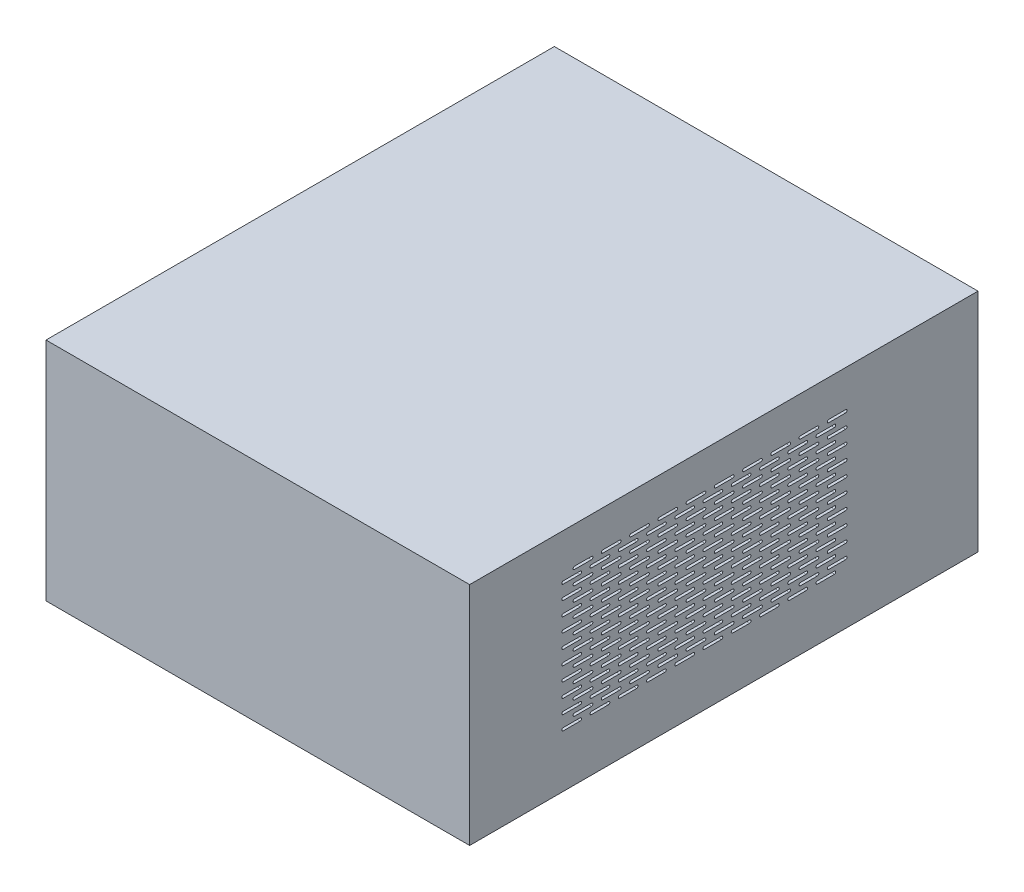
SolidWorks part; units mm, degrees
ref_plane "前视基准面" through (0, 0, 0) normal (0, 0, 1) x (1, 0, 0)
ref_plane "上视基准面" through (0, 0, 0) normal (0, 1, 0) x (1, 0, 0)
ref_plane "右视基准面" through (0, 0, 0) normal (1, 0, 0) x (0, 0, -1)
sketch "草图1" plane through (0, 0, 0) normal (0, 0, 1) x (1, 0, 0)
  line L1 (-75, 40) -> (75, 40)
  line L2 (-75, 40) -> (-75, -40)
  line L3 (-75, -40) -> (75, -40)
  line L4 (75, 40) -> (75, -40)
  line L5 (-75, 40) -> (75, -40) construction
  line L6 (-75, -40) -> (75, 40) construction
  point P0 (0, 0)
  dimension "D1" = 150
  dimension "D2" = 80
extrude "凸台-拉伸1" add sketch "草图1" along normal blind 90 and the other way blind 90 contours L1 L4 L3 L2
shell "抽壳1" thickness 2.3 removed face at (0, 0, -90)
sketch "草图2" plane through (75, 0, 0) normal (1, 0, 0) x (0, 0, -1)
  line L0 (-46.8721, 27.0767) -> (-52.8721, 27.0767)
  line L1 (-46.8721, 26.0767) -> (-52.8721, 26.0767)
  line L2 (-36.8721, 27.0767) -> (-42.8721, 27.0767)
  line L3 (-36.8721, 26.0767) -> (-42.8721, 26.0767)
  line L4 (-26.8721, 27.0767) -> (-32.8721, 27.0767)
  line L5 (-26.8721, 26.0767) -> (-32.8721, 26.0767)
  line L6 (-16.8721, 27.0767) -> (-22.8721, 27.0767)
  line L7 (-16.8721, 26.0767) -> (-22.8721, 26.0767)
  line L8 (-6.8721, 27.0767) -> (-12.8721, 27.0767)
  line L9 (-6.8721, 26.0767) -> (-12.8721, 26.0767)
  line L10 (3.1279, 27.0767) -> (-2.8721, 27.0767)
  line L11 (3.1279, 26.0767) -> (-2.8721, 26.0767)
  line L12 (13.1279, 27.0767) -> (7.1279, 27.0767)
  line L13 (13.1279, 26.0767) -> (7.1279, 26.0767)
  line L14 (23.1279, 27.0767) -> (17.1279, 27.0767)
  line L15 (23.1279, 26.0767) -> (17.1279, 26.0767)
  line L16 (33.1279, 27.0767) -> (27.1279, 27.0767)
  line L17 (33.1279, 26.0767) -> (27.1279, 26.0767)
  line L18 (43.1279, 27.0767) -> (37.1279, 27.0767)
  line L19 (43.1279, 26.0767) -> (37.1279, 26.0767)
  line L20 (-50.8721, 24.5767) -> (-56.8721, 24.5767)
  line L21 (-50.8721, 23.5767) -> (-56.8721, 23.5767)
  line L22 (-40.8721, 24.5767) -> (-46.8721, 24.5767)
  line L23 (-40.8721, 23.5767) -> (-46.8721, 23.5767)
  line L24 (-30.8721, 24.5767) -> (-36.8721, 24.5767)
  line L25 (-30.8721, 23.5767) -> (-36.8721, 23.5767)
  line L26 (-20.8721, 24.5767) -> (-26.8721, 24.5767)
  line L27 (-20.8721, 23.5767) -> (-26.8721, 23.5767)
  line L28 (-10.8721, 24.5767) -> (-16.8721, 24.5767)
  line L29 (-10.8721, 23.5767) -> (-16.8721, 23.5767)
  line L30 (-0.8721, 24.5767) -> (-6.8721, 24.5767)
  line L31 (-0.8721, 23.5767) -> (-6.8721, 23.5767)
  line L32 (9.1279, 24.5767) -> (3.1279, 24.5767)
  line L33 (9.1279, 23.5767) -> (3.1279, 23.5767)
  line L34 (19.1279, 24.5767) -> (13.1279, 24.5767)
  line L35 (19.1279, 23.5767) -> (13.1279, 23.5767)
  line L36 (29.1279, 24.5767) -> (23.1279, 24.5767)
  line L37 (29.1279, 23.5767) -> (23.1279, 23.5767)
  line L38 (39.1279, 24.5767) -> (33.1279, 24.5767)
  line L39 (39.1279, 23.5767) -> (33.1279, 23.5767)
  line L40 (-46.8721, 22.0767) -> (-52.8721, 22.0767)
  line L41 (-46.8721, 21.0767) -> (-52.8721, 21.0767)
  line L42 (-36.8721, 22.0767) -> (-42.8721, 22.0767)
  line L43 (-36.8721, 21.0767) -> (-42.8721, 21.0767)
  line L44 (-26.8721, 22.0767) -> (-32.8721, 22.0767)
  line L45 (-26.8721, 21.0767) -> (-32.8721, 21.0767)
  line L46 (-16.8721, 22.0767) -> (-22.8721, 22.0767)
  line L47 (-16.8721, 21.0767) -> (-22.8721, 21.0767)
  line L48 (-6.8721, 22.0767) -> (-12.8721, 22.0767)
  line L49 (-6.8721, 21.0767) -> (-12.8721, 21.0767)
  line L50 (3.1279, 22.0767) -> (-2.8721, 22.0767)
  line L51 (3.1279, 21.0767) -> (-2.8721, 21.0767)
  line L52 (13.1279, 22.0767) -> (7.1279, 22.0767)
  line L53 (13.1279, 21.0767) -> (7.1279, 21.0767)
  line L54 (23.1279, 22.0767) -> (17.1279, 22.0767)
  line L55 (23.1279, 21.0767) -> (17.1279, 21.0767)
  line L56 (33.1279, 22.0767) -> (27.1279, 22.0767)
  line L57 (33.1279, 21.0767) -> (27.1279, 21.0767)
  line L58 (43.1279, 22.0767) -> (37.1279, 22.0767)
  line L59 (43.1279, 21.0767) -> (37.1279, 21.0767)
  line L60 (-50.8721, 19.5767) -> (-56.8721, 19.5767)
  line L61 (-50.8721, 18.5767) -> (-56.8721, 18.5767)
  line L62 (-40.8721, 19.5767) -> (-46.8721, 19.5767)
  line L63 (-40.8721, 18.5767) -> (-46.8721, 18.5767)
  line L64 (-30.8721, 19.5767) -> (-36.8721, 19.5767)
  line L65 (-30.8721, 18.5767) -> (-36.8721, 18.5767)
  line L66 (-20.8721, 19.5767) -> (-26.8721, 19.5767)
  line L67 (-20.8721, 18.5767) -> (-26.8721, 18.5767)
  line L68 (-10.8721, 19.5767) -> (-16.8721, 19.5767)
  line L69 (-10.8721, 18.5767) -> (-16.8721, 18.5767)
  line L70 (-0.8721, 19.5767) -> (-6.8721, 19.5767)
  line L71 (-0.8721, 18.5767) -> (-6.8721, 18.5767)
  line L72 (9.1279, 19.5767) -> (3.1279, 19.5767)
  line L73 (9.1279, 18.5767) -> (3.1279, 18.5767)
  line L74 (19.1279, 19.5767) -> (13.1279, 19.5767)
  line L75 (19.1279, 18.5767) -> (13.1279, 18.5767)
  line L76 (29.1279, 19.5767) -> (23.1279, 19.5767)
  line L77 (29.1279, 18.5767) -> (23.1279, 18.5767)
  line L78 (39.1279, 19.5767) -> (33.1279, 19.5767)
  line L79 (39.1279, 18.5767) -> (33.1279, 18.5767)
  line L80 (-46.8721, 17.0767) -> (-52.8721, 17.0767)
  line L81 (-46.8721, 16.0767) -> (-52.8721, 16.0767)
  line L82 (-36.8721, 17.0767) -> (-42.8721, 17.0767)
  line L83 (-36.8721, 16.0767) -> (-42.8721, 16.0767)
  line L84 (-26.8721, 17.0767) -> (-32.8721, 17.0767)
  line L85 (-26.8721, 16.0767) -> (-32.8721, 16.0767)
  line L86 (-16.8721, 17.0767) -> (-22.8721, 17.0767)
  line L87 (-16.8721, 16.0767) -> (-22.8721, 16.0767)
  line L88 (-6.8721, 17.0767) -> (-12.8721, 17.0767)
  line L89 (-6.8721, 16.0767) -> (-12.8721, 16.0767)
  line L90 (3.1279, 17.0767) -> (-2.8721, 17.0767)
  line L91 (3.1279, 16.0767) -> (-2.8721, 16.0767)
  line L92 (13.1279, 17.0767) -> (7.1279, 17.0767)
  line L93 (13.1279, 16.0767) -> (7.1279, 16.0767)
  line L94 (23.1279, 17.0767) -> (17.1279, 17.0767)
  line L95 (23.1279, 16.0767) -> (17.1279, 16.0767)
  line L96 (33.1279, 17.0767) -> (27.1279, 17.0767)
  line L97 (33.1279, 16.0767) -> (27.1279, 16.0767)
  line L98 (43.1279, 17.0767) -> (37.1279, 17.0767)
  line L99 (43.1279, 16.0767) -> (37.1279, 16.0767)
  line L100 (-50.8721, 14.5767) -> (-56.8721, 14.5767)
  line L101 (-50.8721, 13.5767) -> (-56.8721, 13.5767)
  line L102 (-40.8721, 14.5767) -> (-46.8721, 14.5767)
  line L103 (-40.8721, 13.5767) -> (-46.8721, 13.5767)
  line L104 (-30.8721, 14.5767) -> (-36.8721, 14.5767)
  line L105 (-30.8721, 13.5767) -> (-36.8721, 13.5767)
  line L106 (-20.8721, 14.5767) -> (-26.8721, 14.5767)
  line L107 (-20.8721, 13.5767) -> (-26.8721, 13.5767)
  line L108 (-10.8721, 14.5767) -> (-16.8721, 14.5767)
  line L109 (-10.8721, 13.5767) -> (-16.8721, 13.5767)
  line L110 (-0.8721, 14.5767) -> (-6.8721, 14.5767)
  line L111 (-0.8721, 13.5767) -> (-6.8721, 13.5767)
  line L112 (9.1279, 14.5767) -> (3.1279, 14.5767)
  line L113 (9.1279, 13.5767) -> (3.1279, 13.5767)
  line L114 (19.1279, 14.5767) -> (13.1279, 14.5767)
  line L115 (19.1279, 13.5767) -> (13.1279, 13.5767)
  line L116 (29.1279, 14.5767) -> (23.1279, 14.5767)
  line L117 (29.1279, 13.5767) -> (23.1279, 13.5767)
  line L118 (39.1279, 14.5767) -> (33.1279, 14.5767)
  line L119 (39.1279, 13.5767) -> (33.1279, 13.5767)
  line L120 (-46.8721, 12.0767) -> (-52.8721, 12.0767)
  line L121 (-46.8721, 11.0767) -> (-52.8721, 11.0767)
  line L122 (-36.8721, 12.0767) -> (-42.8721, 12.0767)
  line L123 (-36.8721, 11.0767) -> (-42.8721, 11.0767)
  line L124 (-26.8721, 12.0767) -> (-32.8721, 12.0767)
  line L125 (-26.8721, 11.0767) -> (-32.8721, 11.0767)
  line L126 (-16.8721, 12.0767) -> (-22.8721, 12.0767)
  line L127 (-16.8721, 11.0767) -> (-22.8721, 11.0767)
  line L128 (-6.8721, 12.0767) -> (-12.8721, 12.0767)
  line L129 (-6.8721, 11.0767) -> (-12.8721, 11.0767)
  line L130 (3.1279, 12.0767) -> (-2.8721, 12.0767)
  line L131 (3.1279, 11.0767) -> (-2.8721, 11.0767)
  line L132 (13.1279, 12.0767) -> (7.1279, 12.0767)
  line L133 (13.1279, 11.0767) -> (7.1279, 11.0767)
  line L134 (23.1279, 12.0767) -> (17.1279, 12.0767)
  line L135 (23.1279, 11.0767) -> (17.1279, 11.0767)
  line L136 (33.1279, 12.0767) -> (27.1279, 12.0767)
  line L137 (33.1279, 11.0767) -> (27.1279, 11.0767)
  line L138 (43.1279, 12.0767) -> (37.1279, 12.0767)
  line L139 (43.1279, 11.0767) -> (37.1279, 11.0767)
  line L140 (-50.8721, 9.5767) -> (-56.8721, 9.5767)
  line L141 (-50.8721, 8.5767) -> (-56.8721, 8.5767)
  line L142 (-40.8721, 9.5767) -> (-46.8721, 9.5767)
  line L143 (-40.8721, 8.5767) -> (-46.8721, 8.5767)
  line L144 (-30.8721, 9.5767) -> (-36.8721, 9.5767)
  line L145 (-30.8721, 8.5767) -> (-36.8721, 8.5767)
  line L146 (-20.8721, 9.5767) -> (-26.8721, 9.5767)
  line L147 (-20.8721, 8.5767) -> (-26.8721, 8.5767)
  line L148 (-10.8721, 9.5767) -> (-16.8721, 9.5767)
  line L149 (-10.8721, 8.5767) -> (-16.8721, 8.5767)
  line L150 (-0.8721, 9.5767) -> (-6.8721, 9.5767)
  line L151 (-0.8721, 8.5767) -> (-6.8721, 8.5767)
  line L152 (9.1279, 9.5767) -> (3.1279, 9.5767)
  line L153 (9.1279, 8.5767) -> (3.1279, 8.5767)
  line L154 (19.1279, 9.5767) -> (13.1279, 9.5767)
  line L155 (19.1279, 8.5767) -> (13.1279, 8.5767)
  line L156 (29.1279, 9.5767) -> (23.1279, 9.5767)
  line L157 (29.1279, 8.5767) -> (23.1279, 8.5767)
  line L158 (39.1279, 9.5767) -> (33.1279, 9.5767)
  line L159 (39.1279, 8.5767) -> (33.1279, 8.5767)
  line L160 (-46.8721, 7.0767) -> (-52.8721, 7.0767)
  line L161 (-46.8721, 6.0767) -> (-52.8721, 6.0767)
  line L162 (-36.8721, 7.0767) -> (-42.8721, 7.0767)
  line L163 (-36.8721, 6.0767) -> (-42.8721, 6.0767)
  line L164 (-26.8721, 7.0767) -> (-32.8721, 7.0767)
  line L165 (-26.8721, 6.0767) -> (-32.8721, 6.0767)
  line L166 (-16.8721, 7.0767) -> (-22.8721, 7.0767)
  line L167 (-16.8721, 6.0767) -> (-22.8721, 6.0767)
  line L168 (-6.8721, 7.0767) -> (-12.8721, 7.0767)
  line L169 (-6.8721, 6.0767) -> (-12.8721, 6.0767)
  line L170 (3.1279, 7.0767) -> (-2.8721, 7.0767)
  line L171 (3.1279, 6.0767) -> (-2.8721, 6.0767)
  line L172 (13.1279, 7.0767) -> (7.1279, 7.0767)
  line L173 (13.1279, 6.0767) -> (7.1279, 6.0767)
  line L174 (23.1279, 7.0767) -> (17.1279, 7.0767)
  line L175 (23.1279, 6.0767) -> (17.1279, 6.0767)
  line L176 (33.1279, 7.0767) -> (27.1279, 7.0767)
  line L177 (33.1279, 6.0767) -> (27.1279, 6.0767)
  line L178 (43.1279, 7.0767) -> (37.1279, 7.0767)
  line L179 (43.1279, 6.0767) -> (37.1279, 6.0767)
  line L180 (-50.8721, 4.5767) -> (-56.8721, 4.5767)
  line L181 (-50.8721, 3.5767) -> (-56.8721, 3.5767)
  line L182 (-40.8721, 4.5767) -> (-46.8721, 4.5767)
  line L183 (-40.8721, 3.5767) -> (-46.8721, 3.5767)
  line L184 (-30.8721, 4.5767) -> (-36.8721, 4.5767)
  line L185 (-30.8721, 3.5767) -> (-36.8721, 3.5767)
  line L186 (-20.8721, 4.5767) -> (-26.8721, 4.5767)
  line L187 (-20.8721, 3.5767) -> (-26.8721, 3.5767)
  line L188 (-10.8721, 4.5767) -> (-16.8721, 4.5767)
  line L189 (-10.8721, 3.5767) -> (-16.8721, 3.5767)
  line L190 (-0.8721, 4.5767) -> (-6.8721, 4.5767)
  line L191 (-0.8721, 3.5767) -> (-6.8721, 3.5767)
  line L192 (9.1279, 4.5767) -> (3.1279, 4.5767)
  line L193 (9.1279, 3.5767) -> (3.1279, 3.5767)
  line L194 (19.1279, 4.5767) -> (13.1279, 4.5767)
  line L195 (19.1279, 3.5767) -> (13.1279, 3.5767)
  line L196 (29.1279, 4.5767) -> (23.1279, 4.5767)
  line L197 (29.1279, 3.5767) -> (23.1279, 3.5767)
  line L198 (39.1279, 4.5767) -> (33.1279, 4.5767)
  line L199 (39.1279, 3.5767) -> (33.1279, 3.5767)
  line L200 (-46.8721, 2.0767) -> (-52.8721, 2.0767)
  line L201 (-46.8721, 1.0767) -> (-52.8721, 1.0767)
  line L202 (-36.8721, 2.0767) -> (-42.8721, 2.0767)
  line L203 (-36.8721, 1.0767) -> (-42.8721, 1.0767)
  line L204 (-26.8721, 2.0767) -> (-32.8721, 2.0767)
  line L205 (-26.8721, 1.0767) -> (-32.8721, 1.0767)
  line L206 (-16.8721, 2.0767) -> (-22.8721, 2.0767)
  line L207 (-16.8721, 1.0767) -> (-22.8721, 1.0767)
  line L208 (-6.8721, 2.0767) -> (-12.8721, 2.0767)
  line L209 (-6.8721, 1.0767) -> (-12.8721, 1.0767)
  line L210 (3.1279, 2.0767) -> (-2.8721, 2.0767)
  line L211 (3.1279, 1.0767) -> (-2.8721, 1.0767)
  line L212 (13.1279, 2.0767) -> (7.1279, 2.0767)
  line L213 (13.1279, 1.0767) -> (7.1279, 1.0767)
  line L214 (23.1279, 2.0767) -> (17.1279, 2.0767)
  line L215 (23.1279, 1.0767) -> (17.1279, 1.0767)
  line L216 (33.1279, 2.0767) -> (27.1279, 2.0767)
  line L217 (33.1279, 1.0767) -> (27.1279, 1.0767)
  line L218 (43.1279, 2.0767) -> (37.1279, 2.0767)
  line L219 (43.1279, 1.0767) -> (37.1279, 1.0767)
  line L220 (-50.8721, -0.4233) -> (-56.8721, -0.4233)
  line L221 (-50.8721, -1.4233) -> (-56.8721, -1.4233)
  line L222 (-40.8721, -0.4233) -> (-46.8721, -0.4233)
  line L223 (-40.8721, -1.4233) -> (-46.8721, -1.4233)
  line L224 (-30.8721, -0.4233) -> (-36.8721, -0.4233)
  line L225 (-30.8721, -1.4233) -> (-36.8721, -1.4233)
  line L226 (-20.8721, -0.4233) -> (-26.8721, -0.4233)
  line L227 (-20.8721, -1.4233) -> (-26.8721, -1.4233)
  line L228 (-10.8721, -0.4233) -> (-16.8721, -0.4233)
  line L229 (-10.8721, -1.4233) -> (-16.8721, -1.4233)
  line L230 (-0.8721, -0.4233) -> (-6.8721, -0.4233)
  line L231 (-0.8721, -1.4233) -> (-6.8721, -1.4233)
  line L232 (9.1279, -0.4233) -> (3.1279, -0.4233)
  line L233 (9.1279, -1.4233) -> (3.1279, -1.4233)
  line L234 (19.1279, -0.4233) -> (13.1279, -0.4233)
  line L235 (19.1279, -1.4233) -> (13.1279, -1.4233)
  line L236 (29.1279, -0.4233) -> (23.1279, -0.4233)
  line L237 (29.1279, -1.4233) -> (23.1279, -1.4233)
  line L238 (39.1279, -0.4233) -> (33.1279, -0.4233)
  line L239 (39.1279, -1.4233) -> (33.1279, -1.4233)
  line L240 (-46.8721, -2.9233) -> (-52.8721, -2.9233)
  line L241 (-46.8721, -3.9233) -> (-52.8721, -3.9233)
  line L242 (-36.8721, -2.9233) -> (-42.8721, -2.9233)
  line L243 (-36.8721, -3.9233) -> (-42.8721, -3.9233)
  line L244 (-26.8721, -2.9233) -> (-32.8721, -2.9233)
  line L245 (-26.8721, -3.9233) -> (-32.8721, -3.9233)
  line L246 (-16.8721, -2.9233) -> (-22.8721, -2.9233)
  line L247 (-16.8721, -3.9233) -> (-22.8721, -3.9233)
  line L248 (-6.8721, -2.9233) -> (-12.8721, -2.9233)
  line L249 (-6.8721, -3.9233) -> (-12.8721, -3.9233)
  line L250 (3.1279, -2.9233) -> (-2.8721, -2.9233)
  line L251 (3.1279, -3.9233) -> (-2.8721, -3.9233)
  line L252 (13.1279, -2.9233) -> (7.1279, -2.9233)
  line L253 (13.1279, -3.9233) -> (7.1279, -3.9233)
  line L254 (23.1279, -2.9233) -> (17.1279, -2.9233)
  line L255 (23.1279, -3.9233) -> (17.1279, -3.9233)
  line L256 (33.1279, -2.9233) -> (27.1279, -2.9233)
  line L257 (33.1279, -3.9233) -> (27.1279, -3.9233)
  line L258 (43.1279, -2.9233) -> (37.1279, -2.9233)
  line L259 (43.1279, -3.9233) -> (37.1279, -3.9233)
  line L260 (-50.8721, -5.4233) -> (-56.8721, -5.4233)
  line L261 (-50.8721, -6.4233) -> (-56.8721, -6.4233)
  line L262 (-40.8721, -5.4233) -> (-46.8721, -5.4233)
  line L263 (-40.8721, -6.4233) -> (-46.8721, -6.4233)
  line L264 (-30.8721, -5.4233) -> (-36.8721, -5.4233)
  line L265 (-30.8721, -6.4233) -> (-36.8721, -6.4233)
  line L266 (-20.8721, -5.4233) -> (-26.8721, -5.4233)
  line L267 (-20.8721, -6.4233) -> (-26.8721, -6.4233)
  line L268 (-10.8721, -5.4233) -> (-16.8721, -5.4233)
  line L269 (-10.8721, -6.4233) -> (-16.8721, -6.4233)
  line L270 (-0.8721, -5.4233) -> (-6.8721, -5.4233)
  line L271 (-0.8721, -6.4233) -> (-6.8721, -6.4233)
  line L272 (9.1279, -5.4233) -> (3.1279, -5.4233)
  line L273 (9.1279, -6.4233) -> (3.1279, -6.4233)
  line L274 (19.1279, -5.4233) -> (13.1279, -5.4233)
  line L275 (19.1279, -6.4233) -> (13.1279, -6.4233)
  line L276 (29.1279, -5.4233) -> (23.1279, -5.4233)
  line L277 (29.1279, -6.4233) -> (23.1279, -6.4233)
  line L278 (39.1279, -5.4233) -> (33.1279, -5.4233)
  line L279 (39.1279, -6.4233) -> (33.1279, -6.4233)
  line L280 (-46.8721, -7.9233) -> (-52.8721, -7.9233)
  line L281 (-46.8721, -8.9233) -> (-52.8721, -8.9233)
  line L282 (-36.8721, -7.9233) -> (-42.8721, -7.9233)
  line L283 (-36.8721, -8.9233) -> (-42.8721, -8.9233)
  line L284 (-26.8721, -7.9233) -> (-32.8721, -7.9233)
  line L285 (-26.8721, -8.9233) -> (-32.8721, -8.9233)
  line L286 (-16.8721, -7.9233) -> (-22.8721, -7.9233)
  line L287 (-16.8721, -8.9233) -> (-22.8721, -8.9233)
  line L288 (-6.8721, -7.9233) -> (-12.8721, -7.9233)
  line L289 (-6.8721, -8.9233) -> (-12.8721, -8.9233)
  line L290 (3.1279, -7.9233) -> (-2.8721, -7.9233)
  line L291 (3.1279, -8.9233) -> (-2.8721, -8.9233)
  line L292 (13.1279, -7.9233) -> (7.1279, -7.9233)
  line L293 (13.1279, -8.9233) -> (7.1279, -8.9233)
  line L294 (23.1279, -7.9233) -> (17.1279, -7.9233)
  line L295 (23.1279, -8.9233) -> (17.1279, -8.9233)
  line L296 (33.1279, -7.9233) -> (27.1279, -7.9233)
  line L297 (33.1279, -8.9233) -> (27.1279, -8.9233)
  line L298 (43.1279, -7.9233) -> (37.1279, -7.9233)
  line L299 (43.1279, -8.9233) -> (37.1279, -8.9233)
  line L300 (-50.8721, -10.4233) -> (-56.8721, -10.4233)
  line L301 (-50.8721, -11.4233) -> (-56.8721, -11.4233)
  line L302 (-40.8721, -10.4233) -> (-46.8721, -10.4233)
  line L303 (-40.8721, -11.4233) -> (-46.8721, -11.4233)
  line L304 (-30.8721, -10.4233) -> (-36.8721, -10.4233)
  line L305 (-30.8721, -11.4233) -> (-36.8721, -11.4233)
  line L306 (-20.8721, -10.4233) -> (-26.8721, -10.4233)
  line L307 (-20.8721, -11.4233) -> (-26.8721, -11.4233)
  line L308 (-10.8721, -10.4233) -> (-16.8721, -10.4233)
  line L309 (-10.8721, -11.4233) -> (-16.8721, -11.4233)
  line L310 (-0.8721, -10.4233) -> (-6.8721, -10.4233)
  line L311 (-0.8721, -11.4233) -> (-6.8721, -11.4233)
  line L312 (9.1279, -10.4233) -> (3.1279, -10.4233)
  line L313 (9.1279, -11.4233) -> (3.1279, -11.4233)
  line L314 (19.1279, -10.4233) -> (13.1279, -10.4233)
  line L315 (19.1279, -11.4233) -> (13.1279, -11.4233)
  line L316 (29.1279, -10.4233) -> (23.1279, -10.4233)
  line L317 (29.1279, -11.4233) -> (23.1279, -11.4233)
  line L318 (39.1279, -10.4233) -> (33.1279, -10.4233)
  line L319 (39.1279, -11.4233) -> (33.1279, -11.4233)
  line L320 (-46.8721, -12.9233) -> (-52.8721, -12.9233)
  line L321 (-46.8721, -13.9233) -> (-52.8721, -13.9233)
  line L322 (-36.8721, -12.9233) -> (-42.8721, -12.9233)
  line L323 (-36.8721, -13.9233) -> (-42.8721, -13.9233)
  line L324 (-26.8721, -12.9233) -> (-32.8721, -12.9233)
  line L325 (-26.8721, -13.9233) -> (-32.8721, -13.9233)
  line L326 (-16.8721, -12.9233) -> (-22.8721, -12.9233)
  line L327 (-16.8721, -13.9233) -> (-22.8721, -13.9233)
  line L328 (-6.8721, -12.9233) -> (-12.8721, -12.9233)
  line L329 (-6.8721, -13.9233) -> (-12.8721, -13.9233)
  line L330 (3.1279, -12.9233) -> (-2.8721, -12.9233)
  line L331 (3.1279, -13.9233) -> (-2.8721, -13.9233)
  line L332 (13.1279, -12.9233) -> (7.1279, -12.9233)
  line L333 (13.1279, -13.9233) -> (7.1279, -13.9233)
  line L334 (23.1279, -12.9233) -> (17.1279, -12.9233)
  line L335 (23.1279, -13.9233) -> (17.1279, -13.9233)
  line L336 (33.1279, -12.9233) -> (27.1279, -12.9233)
  line L337 (33.1279, -13.9233) -> (27.1279, -13.9233)
  line L338 (43.1279, -12.9233) -> (37.1279, -12.9233)
  line L339 (43.1279, -13.9233) -> (37.1279, -13.9233)
  line L340 (-50.8721, -15.4233) -> (-56.8721, -15.4233)
  line L341 (-50.8721, -16.4233) -> (-56.8721, -16.4233)
  line L342 (-40.8721, -15.4233) -> (-46.8721, -15.4233)
  line L343 (-40.8721, -16.4233) -> (-46.8721, -16.4233)
  line L344 (-30.8721, -15.4233) -> (-36.8721, -15.4233)
  line L345 (-30.8721, -16.4233) -> (-36.8721, -16.4233)
  line L346 (-20.8721, -15.4233) -> (-26.8721, -15.4233)
  line L347 (-20.8721, -16.4233) -> (-26.8721, -16.4233)
  line L348 (-10.8721, -15.4233) -> (-16.8721, -15.4233)
  line L349 (-10.8721, -16.4233) -> (-16.8721, -16.4233)
  line L350 (-0.8721, -15.4233) -> (-6.8721, -15.4233)
  line L351 (-0.8721, -16.4233) -> (-6.8721, -16.4233)
  line L352 (9.1279, -15.4233) -> (3.1279, -15.4233)
  line L353 (9.1279, -16.4233) -> (3.1279, -16.4233)
  line L354 (19.1279, -15.4233) -> (13.1279, -15.4233)
  line L355 (19.1279, -16.4233) -> (13.1279, -16.4233)
  line L356 (29.1279, -15.4233) -> (23.1279, -15.4233)
  line L357 (29.1279, -16.4233) -> (23.1279, -16.4233)
  line L358 (39.1279, -15.4233) -> (33.1279, -15.4233)
  line L359 (39.1279, -16.4233) -> (33.1279, -16.4233)
  line L360 (-46.8721, -17.9233) -> (-52.8721, -17.9233)
  line L361 (-46.8721, -18.9233) -> (-52.8721, -18.9233)
  line L362 (-36.8721, -17.9233) -> (-42.8721, -17.9233)
  line L363 (-36.8721, -18.9233) -> (-42.8721, -18.9233)
  line L364 (-26.8721, -17.9233) -> (-32.8721, -17.9233)
  line L365 (-26.8721, -18.9233) -> (-32.8721, -18.9233)
  line L366 (-16.8721, -17.9233) -> (-22.8721, -17.9233)
  line L367 (-16.8721, -18.9233) -> (-22.8721, -18.9233)
  line L368 (-6.8721, -17.9233) -> (-12.8721, -17.9233)
  line L369 (-6.8721, -18.9233) -> (-12.8721, -18.9233)
  line L370 (3.1279, -17.9233) -> (-2.8721, -17.9233)
  line L371 (3.1279, -18.9233) -> (-2.8721, -18.9233)
  line L372 (13.1279, -17.9233) -> (7.1279, -17.9233)
  line L373 (13.1279, -18.9233) -> (7.1279, -18.9233)
  line L374 (23.1279, -17.9233) -> (17.1279, -17.9233)
  line L375 (23.1279, -18.9233) -> (17.1279, -18.9233)
  line L376 (33.1279, -17.9233) -> (27.1279, -17.9233)
  line L377 (33.1279, -18.9233) -> (27.1279, -18.9233)
  line L378 (43.1279, -17.9233) -> (37.1279, -17.9233)
  line L379 (43.1279, -18.9233) -> (37.1279, -18.9233)
  line L380 (-50.8721, -20.4233) -> (-56.8721, -20.4233)
  line L381 (-50.8721, -21.4233) -> (-56.8721, -21.4233)
  line L382 (-40.8721, -20.4233) -> (-46.8721, -20.4233)
  line L383 (-40.8721, -21.4233) -> (-46.8721, -21.4233)
  line L384 (-30.8721, -20.4233) -> (-36.8721, -20.4233)
  line L385 (-30.8721, -21.4233) -> (-36.8721, -21.4233)
  line L386 (-20.8721, -20.4233) -> (-26.8721, -20.4233)
  line L387 (-20.8721, -21.4233) -> (-26.8721, -21.4233)
  line L388 (-10.8721, -20.4233) -> (-16.8721, -20.4233)
  line L389 (-10.8721, -21.4233) -> (-16.8721, -21.4233)
  line L390 (-0.8721, -20.4233) -> (-6.8721, -20.4233)
  line L391 (-0.8721, -21.4233) -> (-6.8721, -21.4233)
  line L392 (9.1279, -20.4233) -> (3.1279, -20.4233)
  line L393 (9.1279, -21.4233) -> (3.1279, -21.4233)
  line L394 (19.1279, -20.4233) -> (13.1279, -20.4233)
  line L395 (19.1279, -21.4233) -> (13.1279, -21.4233)
  line L396 (29.1279, -20.4233) -> (23.1279, -20.4233)
  line L397 (29.1279, -21.4233) -> (23.1279, -21.4233)
  line L398 (39.1279, -20.4233) -> (33.1279, -20.4233)
  line L399 (39.1279, -21.4233) -> (33.1279, -21.4233)
  arc A0 (-46.8721, 26.0767) -> (-46.8721, 27.0767) centre (-46.8721, 26.5767) ccw
  arc A1 (-52.8721, 27.0767) -> (-52.8721, 26.0767) centre (-52.8721, 26.5767) ccw
  arc A2 (-36.8721, 26.0767) -> (-36.8721, 27.0767) centre (-36.8721, 26.5767) ccw
  arc A3 (-42.8721, 27.0767) -> (-42.8721, 26.0767) centre (-42.8721, 26.5767) ccw
  arc A4 (-26.8721, 26.0767) -> (-26.8721, 27.0767) centre (-26.8721, 26.5767) ccw
  arc A5 (-32.8721, 27.0767) -> (-32.8721, 26.0767) centre (-32.8721, 26.5767) ccw
  arc A6 (-16.8721, 26.0767) -> (-16.8721, 27.0767) centre (-16.8721, 26.5767) ccw
  arc A7 (-22.8721, 27.0767) -> (-22.8721, 26.0767) centre (-22.8721, 26.5767) ccw
  arc A8 (-6.8721, 26.0767) -> (-6.8721, 27.0767) centre (-6.8721, 26.5767) ccw
  arc A9 (-12.8721, 27.0767) -> (-12.8721, 26.0767) centre (-12.8721, 26.5767) ccw
  arc A10 (3.1279, 26.0767) -> (3.1279, 27.0767) centre (3.1279, 26.5767) ccw
  arc A11 (-2.8721, 27.0767) -> (-2.8721, 26.0767) centre (-2.8721, 26.5767) ccw
  arc A12 (13.1279, 26.0767) -> (13.1279, 27.0767) centre (13.1279, 26.5767) ccw
  arc A13 (7.1279, 27.0767) -> (7.1279, 26.0767) centre (7.1279, 26.5767) ccw
  arc A14 (23.1279, 26.0767) -> (23.1279, 27.0767) centre (23.1279, 26.5767) ccw
  arc A15 (17.1279, 27.0767) -> (17.1279, 26.0767) centre (17.1279, 26.5767) ccw
  arc A16 (33.1279, 26.0767) -> (33.1279, 27.0767) centre (33.1279, 26.5767) ccw
  arc A17 (27.1279, 27.0767) -> (27.1279, 26.0767) centre (27.1279, 26.5767) ccw
  arc A18 (43.1279, 26.0767) -> (43.1279, 27.0767) centre (43.1279, 26.5767) ccw
  arc A19 (37.1279, 27.0767) -> (37.1279, 26.0767) centre (37.1279, 26.5767) ccw
  arc A20 (-50.8721, 23.5767) -> (-50.8721, 24.5767) centre (-50.8721, 24.0767) ccw
  arc A21 (-56.8721, 24.5767) -> (-56.8721, 23.5767) centre (-56.8721, 24.0767) ccw
  arc A22 (-40.8721, 23.5767) -> (-40.8721, 24.5767) centre (-40.8721, 24.0767) ccw
  arc A23 (-46.8721, 24.5767) -> (-46.8721, 23.5767) centre (-46.8721, 24.0767) ccw
  arc A24 (-30.8721, 23.5767) -> (-30.8721, 24.5767) centre (-30.8721, 24.0767) ccw
  arc A25 (-36.8721, 24.5767) -> (-36.8721, 23.5767) centre (-36.8721, 24.0767) ccw
  arc A26 (-20.8721, 23.5767) -> (-20.8721, 24.5767) centre (-20.8721, 24.0767) ccw
  arc A27 (-26.8721, 24.5767) -> (-26.8721, 23.5767) centre (-26.8721, 24.0767) ccw
  arc A28 (-10.8721, 23.5767) -> (-10.8721, 24.5767) centre (-10.8721, 24.0767) ccw
  arc A29 (-16.8721, 24.5767) -> (-16.8721, 23.5767) centre (-16.8721, 24.0767) ccw
  arc A30 (-0.8721, 23.5767) -> (-0.8721, 24.5767) centre (-0.8721, 24.0767) ccw
  arc A31 (-6.8721, 24.5767) -> (-6.8721, 23.5767) centre (-6.8721, 24.0767) ccw
  arc A32 (9.1279, 23.5767) -> (9.1279, 24.5767) centre (9.1279, 24.0767) ccw
  arc A33 (3.1279, 24.5767) -> (3.1279, 23.5767) centre (3.1279, 24.0767) ccw
  arc A34 (19.1279, 23.5767) -> (19.1279, 24.5767) centre (19.1279, 24.0767) ccw
  arc A35 (13.1279, 24.5767) -> (13.1279, 23.5767) centre (13.1279, 24.0767) ccw
  arc A36 (29.1279, 23.5767) -> (29.1279, 24.5767) centre (29.1279, 24.0767) ccw
  arc A37 (23.1279, 24.5767) -> (23.1279, 23.5767) centre (23.1279, 24.0767) ccw
  arc A38 (39.1279, 23.5767) -> (39.1279, 24.5767) centre (39.1279, 24.0767) ccw
  arc A39 (33.1279, 24.5767) -> (33.1279, 23.5767) centre (33.1279, 24.0767) ccw
  arc A40 (-46.8721, 21.0767) -> (-46.8721, 22.0767) centre (-46.8721, 21.5767) ccw
  arc A41 (-52.8721, 22.0767) -> (-52.8721, 21.0767) centre (-52.8721, 21.5767) ccw
  arc A42 (-36.8721, 21.0767) -> (-36.8721, 22.0767) centre (-36.8721, 21.5767) ccw
  arc A43 (-42.8721, 22.0767) -> (-42.8721, 21.0767) centre (-42.8721, 21.5767) ccw
  arc A44 (-26.8721, 21.0767) -> (-26.8721, 22.0767) centre (-26.8721, 21.5767) ccw
  arc A45 (-32.8721, 22.0767) -> (-32.8721, 21.0767) centre (-32.8721, 21.5767) ccw
  arc A46 (-16.8721, 21.0767) -> (-16.8721, 22.0767) centre (-16.8721, 21.5767) ccw
  arc A47 (-22.8721, 22.0767) -> (-22.8721, 21.0767) centre (-22.8721, 21.5767) ccw
  arc A48 (-6.8721, 21.0767) -> (-6.8721, 22.0767) centre (-6.8721, 21.5767) ccw
  arc A49 (-12.8721, 22.0767) -> (-12.8721, 21.0767) centre (-12.8721, 21.5767) ccw
  arc A50 (3.1279, 21.0767) -> (3.1279, 22.0767) centre (3.1279, 21.5767) ccw
  arc A51 (-2.8721, 22.0767) -> (-2.8721, 21.0767) centre (-2.8721, 21.5767) ccw
  arc A52 (13.1279, 21.0767) -> (13.1279, 22.0767) centre (13.1279, 21.5767) ccw
  arc A53 (7.1279, 22.0767) -> (7.1279, 21.0767) centre (7.1279, 21.5767) ccw
  arc A54 (23.1279, 21.0767) -> (23.1279, 22.0767) centre (23.1279, 21.5767) ccw
  arc A55 (17.1279, 22.0767) -> (17.1279, 21.0767) centre (17.1279, 21.5767) ccw
  arc A56 (33.1279, 21.0767) -> (33.1279, 22.0767) centre (33.1279, 21.5767) ccw
  arc A57 (27.1279, 22.0767) -> (27.1279, 21.0767) centre (27.1279, 21.5767) ccw
  arc A58 (43.1279, 21.0767) -> (43.1279, 22.0767) centre (43.1279, 21.5767) ccw
  arc A59 (37.1279, 22.0767) -> (37.1279, 21.0767) centre (37.1279, 21.5767) ccw
  arc A60 (-50.8721, 18.5767) -> (-50.8721, 19.5767) centre (-50.8721, 19.0767) ccw
  arc A61 (-56.8721, 19.5767) -> (-56.8721, 18.5767) centre (-56.8721, 19.0767) ccw
  arc A62 (-40.8721, 18.5767) -> (-40.8721, 19.5767) centre (-40.8721, 19.0767) ccw
  arc A63 (-46.8721, 19.5767) -> (-46.8721, 18.5767) centre (-46.8721, 19.0767) ccw
  arc A64 (-30.8721, 18.5767) -> (-30.8721, 19.5767) centre (-30.8721, 19.0767) ccw
  arc A65 (-36.8721, 19.5767) -> (-36.8721, 18.5767) centre (-36.8721, 19.0767) ccw
  arc A66 (-20.8721, 18.5767) -> (-20.8721, 19.5767) centre (-20.8721, 19.0767) ccw
  arc A67 (-26.8721, 19.5767) -> (-26.8721, 18.5767) centre (-26.8721, 19.0767) ccw
  arc A68 (-10.8721, 18.5767) -> (-10.8721, 19.5767) centre (-10.8721, 19.0767) ccw
  arc A69 (-16.8721, 19.5767) -> (-16.8721, 18.5767) centre (-16.8721, 19.0767) ccw
  arc A70 (-0.8721, 18.5767) -> (-0.8721, 19.5767) centre (-0.8721, 19.0767) ccw
  arc A71 (-6.8721, 19.5767) -> (-6.8721, 18.5767) centre (-6.8721, 19.0767) ccw
  arc A72 (9.1279, 18.5767) -> (9.1279, 19.5767) centre (9.1279, 19.0767) ccw
  arc A73 (3.1279, 19.5767) -> (3.1279, 18.5767) centre (3.1279, 19.0767) ccw
  arc A74 (19.1279, 18.5767) -> (19.1279, 19.5767) centre (19.1279, 19.0767) ccw
  arc A75 (13.1279, 19.5767) -> (13.1279, 18.5767) centre (13.1279, 19.0767) ccw
  arc A76 (29.1279, 18.5767) -> (29.1279, 19.5767) centre (29.1279, 19.0767) ccw
  arc A77 (23.1279, 19.5767) -> (23.1279, 18.5767) centre (23.1279, 19.0767) ccw
  arc A78 (39.1279, 18.5767) -> (39.1279, 19.5767) centre (39.1279, 19.0767) ccw
  arc A79 (33.1279, 19.5767) -> (33.1279, 18.5767) centre (33.1279, 19.0767) ccw
  arc A80 (-46.8721, 16.0767) -> (-46.8721, 17.0767) centre (-46.8721, 16.5767) ccw
  arc A81 (-52.8721, 17.0767) -> (-52.8721, 16.0767) centre (-52.8721, 16.5767) ccw
  arc A82 (-36.8721, 16.0767) -> (-36.8721, 17.0767) centre (-36.8721, 16.5767) ccw
  arc A83 (-42.8721, 17.0767) -> (-42.8721, 16.0767) centre (-42.8721, 16.5767) ccw
  arc A84 (-26.8721, 16.0767) -> (-26.8721, 17.0767) centre (-26.8721, 16.5767) ccw
  arc A85 (-32.8721, 17.0767) -> (-32.8721, 16.0767) centre (-32.8721, 16.5767) ccw
  arc A86 (-16.8721, 16.0767) -> (-16.8721, 17.0767) centre (-16.8721, 16.5767) ccw
  arc A87 (-22.8721, 17.0767) -> (-22.8721, 16.0767) centre (-22.8721, 16.5767) ccw
  arc A88 (-6.8721, 16.0767) -> (-6.8721, 17.0767) centre (-6.8721, 16.5767) ccw
  arc A89 (-12.8721, 17.0767) -> (-12.8721, 16.0767) centre (-12.8721, 16.5767) ccw
  arc A90 (3.1279, 16.0767) -> (3.1279, 17.0767) centre (3.1279, 16.5767) ccw
  arc A91 (-2.8721, 17.0767) -> (-2.8721, 16.0767) centre (-2.8721, 16.5767) ccw
  arc A92 (13.1279, 16.0767) -> (13.1279, 17.0767) centre (13.1279, 16.5767) ccw
  arc A93 (7.1279, 17.0767) -> (7.1279, 16.0767) centre (7.1279, 16.5767) ccw
  arc A94 (23.1279, 16.0767) -> (23.1279, 17.0767) centre (23.1279, 16.5767) ccw
  arc A95 (17.1279, 17.0767) -> (17.1279, 16.0767) centre (17.1279, 16.5767) ccw
  arc A96 (33.1279, 16.0767) -> (33.1279, 17.0767) centre (33.1279, 16.5767) ccw
  arc A97 (27.1279, 17.0767) -> (27.1279, 16.0767) centre (27.1279, 16.5767) ccw
  arc A98 (43.1279, 16.0767) -> (43.1279, 17.0767) centre (43.1279, 16.5767) ccw
  arc A99 (37.1279, 17.0767) -> (37.1279, 16.0767) centre (37.1279, 16.5767) ccw
  arc A100 (-50.8721, 13.5767) -> (-50.8721, 14.5767) centre (-50.8721, 14.0767) ccw
  arc A101 (-56.8721, 14.5767) -> (-56.8721, 13.5767) centre (-56.8721, 14.0767) ccw
  arc A102 (-40.8721, 13.5767) -> (-40.8721, 14.5767) centre (-40.8721, 14.0767) ccw
  arc A103 (-46.8721, 14.5767) -> (-46.8721, 13.5767) centre (-46.8721, 14.0767) ccw
  arc A104 (-30.8721, 13.5767) -> (-30.8721, 14.5767) centre (-30.8721, 14.0767) ccw
  arc A105 (-36.8721, 14.5767) -> (-36.8721, 13.5767) centre (-36.8721, 14.0767) ccw
  arc A106 (-20.8721, 13.5767) -> (-20.8721, 14.5767) centre (-20.8721, 14.0767) ccw
  arc A107 (-26.8721, 14.5767) -> (-26.8721, 13.5767) centre (-26.8721, 14.0767) ccw
  arc A108 (-10.8721, 13.5767) -> (-10.8721, 14.5767) centre (-10.8721, 14.0767) ccw
  arc A109 (-16.8721, 14.5767) -> (-16.8721, 13.5767) centre (-16.8721, 14.0767) ccw
  arc A110 (-0.8721, 13.5767) -> (-0.8721, 14.5767) centre (-0.8721, 14.0767) ccw
  arc A111 (-6.8721, 14.5767) -> (-6.8721, 13.5767) centre (-6.8721, 14.0767) ccw
  arc A112 (9.1279, 13.5767) -> (9.1279, 14.5767) centre (9.1279, 14.0767) ccw
  arc A113 (3.1279, 14.5767) -> (3.1279, 13.5767) centre (3.1279, 14.0767) ccw
  arc A114 (19.1279, 13.5767) -> (19.1279, 14.5767) centre (19.1279, 14.0767) ccw
  arc A115 (13.1279, 14.5767) -> (13.1279, 13.5767) centre (13.1279, 14.0767) ccw
  arc A116 (29.1279, 13.5767) -> (29.1279, 14.5767) centre (29.1279, 14.0767) ccw
  arc A117 (23.1279, 14.5767) -> (23.1279, 13.5767) centre (23.1279, 14.0767) ccw
  arc A118 (39.1279, 13.5767) -> (39.1279, 14.5767) centre (39.1279, 14.0767) ccw
  arc A119 (33.1279, 14.5767) -> (33.1279, 13.5767) centre (33.1279, 14.0767) ccw
  arc A120 (-46.8721, 11.0767) -> (-46.8721, 12.0767) centre (-46.8721, 11.5767) ccw
  arc A121 (-52.8721, 12.0767) -> (-52.8721, 11.0767) centre (-52.8721, 11.5767) ccw
  arc A122 (-36.8721, 11.0767) -> (-36.8721, 12.0767) centre (-36.8721, 11.5767) ccw
  arc A123 (-42.8721, 12.0767) -> (-42.8721, 11.0767) centre (-42.8721, 11.5767) ccw
  arc A124 (-26.8721, 11.0767) -> (-26.8721, 12.0767) centre (-26.8721, 11.5767) ccw
  arc A125 (-32.8721, 12.0767) -> (-32.8721, 11.0767) centre (-32.8721, 11.5767) ccw
  arc A126 (-16.8721, 11.0767) -> (-16.8721, 12.0767) centre (-16.8721, 11.5767) ccw
  arc A127 (-22.8721, 12.0767) -> (-22.8721, 11.0767) centre (-22.8721, 11.5767) ccw
  arc A128 (-6.8721, 11.0767) -> (-6.8721, 12.0767) centre (-6.8721, 11.5767) ccw
  arc A129 (-12.8721, 12.0767) -> (-12.8721, 11.0767) centre (-12.8721, 11.5767) ccw
  arc A130 (3.1279, 11.0767) -> (3.1279, 12.0767) centre (3.1279, 11.5767) ccw
  arc A131 (-2.8721, 12.0767) -> (-2.8721, 11.0767) centre (-2.8721, 11.5767) ccw
  arc A132 (13.1279, 11.0767) -> (13.1279, 12.0767) centre (13.1279, 11.5767) ccw
  arc A133 (7.1279, 12.0767) -> (7.1279, 11.0767) centre (7.1279, 11.5767) ccw
  arc A134 (23.1279, 11.0767) -> (23.1279, 12.0767) centre (23.1279, 11.5767) ccw
  arc A135 (17.1279, 12.0767) -> (17.1279, 11.0767) centre (17.1279, 11.5767) ccw
  arc A136 (33.1279, 11.0767) -> (33.1279, 12.0767) centre (33.1279, 11.5767) ccw
  arc A137 (27.1279, 12.0767) -> (27.1279, 11.0767) centre (27.1279, 11.5767) ccw
  arc A138 (43.1279, 11.0767) -> (43.1279, 12.0767) centre (43.1279, 11.5767) ccw
  arc A139 (37.1279, 12.0767) -> (37.1279, 11.0767) centre (37.1279, 11.5767) ccw
  arc A140 (-50.8721, 8.5767) -> (-50.8721, 9.5767) centre (-50.8721, 9.0767) ccw
  arc A141 (-56.8721, 9.5767) -> (-56.8721, 8.5767) centre (-56.8721, 9.0767) ccw
  arc A142 (-40.8721, 8.5767) -> (-40.8721, 9.5767) centre (-40.8721, 9.0767) ccw
  arc A143 (-46.8721, 9.5767) -> (-46.8721, 8.5767) centre (-46.8721, 9.0767) ccw
  arc A144 (-30.8721, 8.5767) -> (-30.8721, 9.5767) centre (-30.8721, 9.0767) ccw
  arc A145 (-36.8721, 9.5767) -> (-36.8721, 8.5767) centre (-36.8721, 9.0767) ccw
  arc A146 (-20.8721, 8.5767) -> (-20.8721, 9.5767) centre (-20.8721, 9.0767) ccw
  arc A147 (-26.8721, 9.5767) -> (-26.8721, 8.5767) centre (-26.8721, 9.0767) ccw
  arc A148 (-10.8721, 8.5767) -> (-10.8721, 9.5767) centre (-10.8721, 9.0767) ccw
  arc A149 (-16.8721, 9.5767) -> (-16.8721, 8.5767) centre (-16.8721, 9.0767) ccw
  arc A150 (-0.8721, 8.5767) -> (-0.8721, 9.5767) centre (-0.8721, 9.0767) ccw
  arc A151 (-6.8721, 9.5767) -> (-6.8721, 8.5767) centre (-6.8721, 9.0767) ccw
  arc A152 (9.1279, 8.5767) -> (9.1279, 9.5767) centre (9.1279, 9.0767) ccw
  arc A153 (3.1279, 9.5767) -> (3.1279, 8.5767) centre (3.1279, 9.0767) ccw
  arc A154 (19.1279, 8.5767) -> (19.1279, 9.5767) centre (19.1279, 9.0767) ccw
  arc A155 (13.1279, 9.5767) -> (13.1279, 8.5767) centre (13.1279, 9.0767) ccw
  arc A156 (29.1279, 8.5767) -> (29.1279, 9.5767) centre (29.1279, 9.0767) ccw
  arc A157 (23.1279, 9.5767) -> (23.1279, 8.5767) centre (23.1279, 9.0767) ccw
  arc A158 (39.1279, 8.5767) -> (39.1279, 9.5767) centre (39.1279, 9.0767) ccw
  arc A159 (33.1279, 9.5767) -> (33.1279, 8.5767) centre (33.1279, 9.0767) ccw
  arc A160 (-46.8721, 6.0767) -> (-46.8721, 7.0767) centre (-46.8721, 6.5767) ccw
  arc A161 (-52.8721, 7.0767) -> (-52.8721, 6.0767) centre (-52.8721, 6.5767) ccw
  arc A162 (-36.8721, 6.0767) -> (-36.8721, 7.0767) centre (-36.8721, 6.5767) ccw
  arc A163 (-42.8721, 7.0767) -> (-42.8721, 6.0767) centre (-42.8721, 6.5767) ccw
  arc A164 (-26.8721, 6.0767) -> (-26.8721, 7.0767) centre (-26.8721, 6.5767) ccw
  arc A165 (-32.8721, 7.0767) -> (-32.8721, 6.0767) centre (-32.8721, 6.5767) ccw
  arc A166 (-16.8721, 6.0767) -> (-16.8721, 7.0767) centre (-16.8721, 6.5767) ccw
  arc A167 (-22.8721, 7.0767) -> (-22.8721, 6.0767) centre (-22.8721, 6.5767) ccw
  arc A168 (-6.8721, 6.0767) -> (-6.8721, 7.0767) centre (-6.8721, 6.5767) ccw
  arc A169 (-12.8721, 7.0767) -> (-12.8721, 6.0767) centre (-12.8721, 6.5767) ccw
  arc A170 (3.1279, 6.0767) -> (3.1279, 7.0767) centre (3.1279, 6.5767) ccw
  arc A171 (-2.8721, 7.0767) -> (-2.8721, 6.0767) centre (-2.8721, 6.5767) ccw
  arc A172 (13.1279, 6.0767) -> (13.1279, 7.0767) centre (13.1279, 6.5767) ccw
  arc A173 (7.1279, 7.0767) -> (7.1279, 6.0767) centre (7.1279, 6.5767) ccw
  arc A174 (23.1279, 6.0767) -> (23.1279, 7.0767) centre (23.1279, 6.5767) ccw
  arc A175 (17.1279, 7.0767) -> (17.1279, 6.0767) centre (17.1279, 6.5767) ccw
  arc A176 (33.1279, 6.0767) -> (33.1279, 7.0767) centre (33.1279, 6.5767) ccw
  arc A177 (27.1279, 7.0767) -> (27.1279, 6.0767) centre (27.1279, 6.5767) ccw
  arc A178 (43.1279, 6.0767) -> (43.1279, 7.0767) centre (43.1279, 6.5767) ccw
  arc A179 (37.1279, 7.0767) -> (37.1279, 6.0767) centre (37.1279, 6.5767) ccw
  arc A180 (-50.8721, 3.5767) -> (-50.8721, 4.5767) centre (-50.8721, 4.0767) ccw
  arc A181 (-56.8721, 4.5767) -> (-56.8721, 3.5767) centre (-56.8721, 4.0767) ccw
  arc A182 (-40.8721, 3.5767) -> (-40.8721, 4.5767) centre (-40.8721, 4.0767) ccw
  arc A183 (-46.8721, 4.5767) -> (-46.8721, 3.5767) centre (-46.8721, 4.0767) ccw
  arc A184 (-30.8721, 3.5767) -> (-30.8721, 4.5767) centre (-30.8721, 4.0767) ccw
  arc A185 (-36.8721, 4.5767) -> (-36.8721, 3.5767) centre (-36.8721, 4.0767) ccw
  arc A186 (-20.8721, 3.5767) -> (-20.8721, 4.5767) centre (-20.8721, 4.0767) ccw
  arc A187 (-26.8721, 4.5767) -> (-26.8721, 3.5767) centre (-26.8721, 4.0767) ccw
  arc A188 (-10.8721, 3.5767) -> (-10.8721, 4.5767) centre (-10.8721, 4.0767) ccw
  arc A189 (-16.8721, 4.5767) -> (-16.8721, 3.5767) centre (-16.8721, 4.0767) ccw
  arc A190 (-0.8721, 3.5767) -> (-0.8721, 4.5767) centre (-0.8721, 4.0767) ccw
  arc A191 (-6.8721, 4.5767) -> (-6.8721, 3.5767) centre (-6.8721, 4.0767) ccw
  arc A192 (9.1279, 3.5767) -> (9.1279, 4.5767) centre (9.1279, 4.0767) ccw
  arc A193 (3.1279, 4.5767) -> (3.1279, 3.5767) centre (3.1279, 4.0767) ccw
  arc A194 (19.1279, 3.5767) -> (19.1279, 4.5767) centre (19.1279, 4.0767) ccw
  arc A195 (13.1279, 4.5767) -> (13.1279, 3.5767) centre (13.1279, 4.0767) ccw
  arc A196 (29.1279, 3.5767) -> (29.1279, 4.5767) centre (29.1279, 4.0767) ccw
  arc A197 (23.1279, 4.5767) -> (23.1279, 3.5767) centre (23.1279, 4.0767) ccw
  arc A198 (39.1279, 3.5767) -> (39.1279, 4.5767) centre (39.1279, 4.0767) ccw
  arc A199 (33.1279, 4.5767) -> (33.1279, 3.5767) centre (33.1279, 4.0767) ccw
  arc A200 (-46.8721, 1.0767) -> (-46.8721, 2.0767) centre (-46.8721, 1.5767) ccw
  arc A201 (-52.8721, 2.0767) -> (-52.8721, 1.0767) centre (-52.8721, 1.5767) ccw
  arc A202 (-36.8721, 1.0767) -> (-36.8721, 2.0767) centre (-36.8721, 1.5767) ccw
  arc A203 (-42.8721, 2.0767) -> (-42.8721, 1.0767) centre (-42.8721, 1.5767) ccw
  arc A204 (-26.8721, 1.0767) -> (-26.8721, 2.0767) centre (-26.8721, 1.5767) ccw
  arc A205 (-32.8721, 2.0767) -> (-32.8721, 1.0767) centre (-32.8721, 1.5767) ccw
  arc A206 (-16.8721, 1.0767) -> (-16.8721, 2.0767) centre (-16.8721, 1.5767) ccw
  arc A207 (-22.8721, 2.0767) -> (-22.8721, 1.0767) centre (-22.8721, 1.5767) ccw
  arc A208 (-6.8721, 1.0767) -> (-6.8721, 2.0767) centre (-6.8721, 1.5767) ccw
  arc A209 (-12.8721, 2.0767) -> (-12.8721, 1.0767) centre (-12.8721, 1.5767) ccw
  arc A210 (3.1279, 1.0767) -> (3.1279, 2.0767) centre (3.1279, 1.5767) ccw
  arc A211 (-2.8721, 2.0767) -> (-2.8721, 1.0767) centre (-2.8721, 1.5767) ccw
  arc A212 (13.1279, 1.0767) -> (13.1279, 2.0767) centre (13.1279, 1.5767) ccw
  arc A213 (7.1279, 2.0767) -> (7.1279, 1.0767) centre (7.1279, 1.5767) ccw
  arc A214 (23.1279, 1.0767) -> (23.1279, 2.0767) centre (23.1279, 1.5767) ccw
  arc A215 (17.1279, 2.0767) -> (17.1279, 1.0767) centre (17.1279, 1.5767) ccw
  arc A216 (33.1279, 1.0767) -> (33.1279, 2.0767) centre (33.1279, 1.5767) ccw
  arc A217 (27.1279, 2.0767) -> (27.1279, 1.0767) centre (27.1279, 1.5767) ccw
  arc A218 (43.1279, 1.0767) -> (43.1279, 2.0767) centre (43.1279, 1.5767) ccw
  arc A219 (37.1279, 2.0767) -> (37.1279, 1.0767) centre (37.1279, 1.5767) ccw
  arc A220 (-50.8721, -1.4233) -> (-50.8721, -0.4233) centre (-50.8721, -0.9233) ccw
  arc A221 (-56.8721, -0.4233) -> (-56.8721, -1.4233) centre (-56.8721, -0.9233) ccw
  arc A222 (-40.8721, -1.4233) -> (-40.8721, -0.4233) centre (-40.8721, -0.9233) ccw
  arc A223 (-46.8721, -0.4233) -> (-46.8721, -1.4233) centre (-46.8721, -0.9233) ccw
  arc A224 (-30.8721, -1.4233) -> (-30.8721, -0.4233) centre (-30.8721, -0.9233) ccw
  arc A225 (-36.8721, -0.4233) -> (-36.8721, -1.4233) centre (-36.8721, -0.9233) ccw
  arc A226 (-20.8721, -1.4233) -> (-20.8721, -0.4233) centre (-20.8721, -0.9233) ccw
  arc A227 (-26.8721, -0.4233) -> (-26.8721, -1.4233) centre (-26.8721, -0.9233) ccw
  arc A228 (-10.8721, -1.4233) -> (-10.8721, -0.4233) centre (-10.8721, -0.9233) ccw
  arc A229 (-16.8721, -0.4233) -> (-16.8721, -1.4233) centre (-16.8721, -0.9233) ccw
  arc A230 (-0.8721, -1.4233) -> (-0.8721, -0.4233) centre (-0.8721, -0.9233) ccw
  arc A231 (-6.8721, -0.4233) -> (-6.8721, -1.4233) centre (-6.8721, -0.9233) ccw
  arc A232 (9.1279, -1.4233) -> (9.1279, -0.4233) centre (9.1279, -0.9233) ccw
  arc A233 (3.1279, -0.4233) -> (3.1279, -1.4233) centre (3.1279, -0.9233) ccw
  arc A234 (19.1279, -1.4233) -> (19.1279, -0.4233) centre (19.1279, -0.9233) ccw
  arc A235 (13.1279, -0.4233) -> (13.1279, -1.4233) centre (13.1279, -0.9233) ccw
  arc A236 (29.1279, -1.4233) -> (29.1279, -0.4233) centre (29.1279, -0.9233) ccw
  arc A237 (23.1279, -0.4233) -> (23.1279, -1.4233) centre (23.1279, -0.9233) ccw
  arc A238 (39.1279, -1.4233) -> (39.1279, -0.4233) centre (39.1279, -0.9233) ccw
  arc A239 (33.1279, -0.4233) -> (33.1279, -1.4233) centre (33.1279, -0.9233) ccw
  arc A240 (-46.8721, -3.9233) -> (-46.8721, -2.9233) centre (-46.8721, -3.4233) ccw
  arc A241 (-52.8721, -2.9233) -> (-52.8721, -3.9233) centre (-52.8721, -3.4233) ccw
  arc A242 (-36.8721, -3.9233) -> (-36.8721, -2.9233) centre (-36.8721, -3.4233) ccw
  arc A243 (-42.8721, -2.9233) -> (-42.8721, -3.9233) centre (-42.8721, -3.4233) ccw
  arc A244 (-26.8721, -3.9233) -> (-26.8721, -2.9233) centre (-26.8721, -3.4233) ccw
  arc A245 (-32.8721, -2.9233) -> (-32.8721, -3.9233) centre (-32.8721, -3.4233) ccw
  arc A246 (-16.8721, -3.9233) -> (-16.8721, -2.9233) centre (-16.8721, -3.4233) ccw
  arc A247 (-22.8721, -2.9233) -> (-22.8721, -3.9233) centre (-22.8721, -3.4233) ccw
  arc A248 (-6.8721, -3.9233) -> (-6.8721, -2.9233) centre (-6.8721, -3.4233) ccw
  arc A249 (-12.8721, -2.9233) -> (-12.8721, -3.9233) centre (-12.8721, -3.4233) ccw
  arc A250 (3.1279, -3.9233) -> (3.1279, -2.9233) centre (3.1279, -3.4233) ccw
  arc A251 (-2.8721, -2.9233) -> (-2.8721, -3.9233) centre (-2.8721, -3.4233) ccw
  arc A252 (13.1279, -3.9233) -> (13.1279, -2.9233) centre (13.1279, -3.4233) ccw
  arc A253 (7.1279, -2.9233) -> (7.1279, -3.9233) centre (7.1279, -3.4233) ccw
  arc A254 (23.1279, -3.9233) -> (23.1279, -2.9233) centre (23.1279, -3.4233) ccw
  arc A255 (17.1279, -2.9233) -> (17.1279, -3.9233) centre (17.1279, -3.4233) ccw
  arc A256 (33.1279, -3.9233) -> (33.1279, -2.9233) centre (33.1279, -3.4233) ccw
  arc A257 (27.1279, -2.9233) -> (27.1279, -3.9233) centre (27.1279, -3.4233) ccw
  arc A258 (43.1279, -3.9233) -> (43.1279, -2.9233) centre (43.1279, -3.4233) ccw
  arc A259 (37.1279, -2.9233) -> (37.1279, -3.9233) centre (37.1279, -3.4233) ccw
  arc A260 (-50.8721, -6.4233) -> (-50.8721, -5.4233) centre (-50.8721, -5.9233) ccw
  arc A261 (-56.8721, -5.4233) -> (-56.8721, -6.4233) centre (-56.8721, -5.9233) ccw
  arc A262 (-40.8721, -6.4233) -> (-40.8721, -5.4233) centre (-40.8721, -5.9233) ccw
  arc A263 (-46.8721, -5.4233) -> (-46.8721, -6.4233) centre (-46.8721, -5.9233) ccw
  arc A264 (-30.8721, -6.4233) -> (-30.8721, -5.4233) centre (-30.8721, -5.9233) ccw
  arc A265 (-36.8721, -5.4233) -> (-36.8721, -6.4233) centre (-36.8721, -5.9233) ccw
  arc A266 (-20.8721, -6.4233) -> (-20.8721, -5.4233) centre (-20.8721, -5.9233) ccw
  arc A267 (-26.8721, -5.4233) -> (-26.8721, -6.4233) centre (-26.8721, -5.9233) ccw
  arc A268 (-10.8721, -6.4233) -> (-10.8721, -5.4233) centre (-10.8721, -5.9233) ccw
  arc A269 (-16.8721, -5.4233) -> (-16.8721, -6.4233) centre (-16.8721, -5.9233) ccw
  arc A270 (-0.8721, -6.4233) -> (-0.8721, -5.4233) centre (-0.8721, -5.9233) ccw
  arc A271 (-6.8721, -5.4233) -> (-6.8721, -6.4233) centre (-6.8721, -5.9233) ccw
  arc A272 (9.1279, -6.4233) -> (9.1279, -5.4233) centre (9.1279, -5.9233) ccw
  arc A273 (3.1279, -5.4233) -> (3.1279, -6.4233) centre (3.1279, -5.9233) ccw
  arc A274 (19.1279, -6.4233) -> (19.1279, -5.4233) centre (19.1279, -5.9233) ccw
  arc A275 (13.1279, -5.4233) -> (13.1279, -6.4233) centre (13.1279, -5.9233) ccw
  arc A276 (29.1279, -6.4233) -> (29.1279, -5.4233) centre (29.1279, -5.9233) ccw
  arc A277 (23.1279, -5.4233) -> (23.1279, -6.4233) centre (23.1279, -5.9233) ccw
  arc A278 (39.1279, -6.4233) -> (39.1279, -5.4233) centre (39.1279, -5.9233) ccw
  arc A279 (33.1279, -5.4233) -> (33.1279, -6.4233) centre (33.1279, -5.9233) ccw
  arc A280 (-46.8721, -8.9233) -> (-46.8721, -7.9233) centre (-46.8721, -8.4233) ccw
  arc A281 (-52.8721, -7.9233) -> (-52.8721, -8.9233) centre (-52.8721, -8.4233) ccw
  arc A282 (-36.8721, -8.9233) -> (-36.8721, -7.9233) centre (-36.8721, -8.4233) ccw
  arc A283 (-42.8721, -7.9233) -> (-42.8721, -8.9233) centre (-42.8721, -8.4233) ccw
  arc A284 (-26.8721, -8.9233) -> (-26.8721, -7.9233) centre (-26.8721, -8.4233) ccw
  arc A285 (-32.8721, -7.9233) -> (-32.8721, -8.9233) centre (-32.8721, -8.4233) ccw
  arc A286 (-16.8721, -8.9233) -> (-16.8721, -7.9233) centre (-16.8721, -8.4233) ccw
  arc A287 (-22.8721, -7.9233) -> (-22.8721, -8.9233) centre (-22.8721, -8.4233) ccw
  arc A288 (-6.8721, -8.9233) -> (-6.8721, -7.9233) centre (-6.8721, -8.4233) ccw
  arc A289 (-12.8721, -7.9233) -> (-12.8721, -8.9233) centre (-12.8721, -8.4233) ccw
  arc A290 (3.1279, -8.9233) -> (3.1279, -7.9233) centre (3.1279, -8.4233) ccw
  arc A291 (-2.8721, -7.9233) -> (-2.8721, -8.9233) centre (-2.8721, -8.4233) ccw
  arc A292 (13.1279, -8.9233) -> (13.1279, -7.9233) centre (13.1279, -8.4233) ccw
  arc A293 (7.1279, -7.9233) -> (7.1279, -8.9233) centre (7.1279, -8.4233) ccw
  arc A294 (23.1279, -8.9233) -> (23.1279, -7.9233) centre (23.1279, -8.4233) ccw
  arc A295 (17.1279, -7.9233) -> (17.1279, -8.9233) centre (17.1279, -8.4233) ccw
  arc A296 (33.1279, -8.9233) -> (33.1279, -7.9233) centre (33.1279, -8.4233) ccw
  arc A297 (27.1279, -7.9233) -> (27.1279, -8.9233) centre (27.1279, -8.4233) ccw
  arc A298 (43.1279, -8.9233) -> (43.1279, -7.9233) centre (43.1279, -8.4233) ccw
  arc A299 (37.1279, -7.9233) -> (37.1279, -8.9233) centre (37.1279, -8.4233) ccw
  arc A300 (-50.8721, -11.4233) -> (-50.8721, -10.4233) centre (-50.8721, -10.9233) ccw
  arc A301 (-56.8721, -10.4233) -> (-56.8721, -11.4233) centre (-56.8721, -10.9233) ccw
  arc A302 (-40.8721, -11.4233) -> (-40.8721, -10.4233) centre (-40.8721, -10.9233) ccw
  arc A303 (-46.8721, -10.4233) -> (-46.8721, -11.4233) centre (-46.8721, -10.9233) ccw
  arc A304 (-30.8721, -11.4233) -> (-30.8721, -10.4233) centre (-30.8721, -10.9233) ccw
  arc A305 (-36.8721, -10.4233) -> (-36.8721, -11.4233) centre (-36.8721, -10.9233) ccw
  arc A306 (-20.8721, -11.4233) -> (-20.8721, -10.4233) centre (-20.8721, -10.9233) ccw
  arc A307 (-26.8721, -10.4233) -> (-26.8721, -11.4233) centre (-26.8721, -10.9233) ccw
  arc A308 (-10.8721, -11.4233) -> (-10.8721, -10.4233) centre (-10.8721, -10.9233) ccw
  arc A309 (-16.8721, -10.4233) -> (-16.8721, -11.4233) centre (-16.8721, -10.9233) ccw
  arc A310 (-0.8721, -11.4233) -> (-0.8721, -10.4233) centre (-0.8721, -10.9233) ccw
  arc A311 (-6.8721, -10.4233) -> (-6.8721, -11.4233) centre (-6.8721, -10.9233) ccw
  arc A312 (9.1279, -11.4233) -> (9.1279, -10.4233) centre (9.1279, -10.9233) ccw
  arc A313 (3.1279, -10.4233) -> (3.1279, -11.4233) centre (3.1279, -10.9233) ccw
  arc A314 (19.1279, -11.4233) -> (19.1279, -10.4233) centre (19.1279, -10.9233) ccw
  arc A315 (13.1279, -10.4233) -> (13.1279, -11.4233) centre (13.1279, -10.9233) ccw
  arc A316 (29.1279, -11.4233) -> (29.1279, -10.4233) centre (29.1279, -10.9233) ccw
  arc A317 (23.1279, -10.4233) -> (23.1279, -11.4233) centre (23.1279, -10.9233) ccw
  arc A318 (39.1279, -11.4233) -> (39.1279, -10.4233) centre (39.1279, -10.9233) ccw
  arc A319 (33.1279, -10.4233) -> (33.1279, -11.4233) centre (33.1279, -10.9233) ccw
  arc A320 (-46.8721, -13.9233) -> (-46.8721, -12.9233) centre (-46.8721, -13.4233) ccw
  arc A321 (-52.8721, -12.9233) -> (-52.8721, -13.9233) centre (-52.8721, -13.4233) ccw
  arc A322 (-36.8721, -13.9233) -> (-36.8721, -12.9233) centre (-36.8721, -13.4233) ccw
  arc A323 (-42.8721, -12.9233) -> (-42.8721, -13.9233) centre (-42.8721, -13.4233) ccw
  arc A324 (-26.8721, -13.9233) -> (-26.8721, -12.9233) centre (-26.8721, -13.4233) ccw
  arc A325 (-32.8721, -12.9233) -> (-32.8721, -13.9233) centre (-32.8721, -13.4233) ccw
  arc A326 (-16.8721, -13.9233) -> (-16.8721, -12.9233) centre (-16.8721, -13.4233) ccw
  arc A327 (-22.8721, -12.9233) -> (-22.8721, -13.9233) centre (-22.8721, -13.4233) ccw
  arc A328 (-6.8721, -13.9233) -> (-6.8721, -12.9233) centre (-6.8721, -13.4233) ccw
  arc A329 (-12.8721, -12.9233) -> (-12.8721, -13.9233) centre (-12.8721, -13.4233) ccw
  arc A330 (3.1279, -13.9233) -> (3.1279, -12.9233) centre (3.1279, -13.4233) ccw
  arc A331 (-2.8721, -12.9233) -> (-2.8721, -13.9233) centre (-2.8721, -13.4233) ccw
  arc A332 (13.1279, -13.9233) -> (13.1279, -12.9233) centre (13.1279, -13.4233) ccw
  arc A333 (7.1279, -12.9233) -> (7.1279, -13.9233) centre (7.1279, -13.4233) ccw
  arc A334 (23.1279, -13.9233) -> (23.1279, -12.9233) centre (23.1279, -13.4233) ccw
  arc A335 (17.1279, -12.9233) -> (17.1279, -13.9233) centre (17.1279, -13.4233) ccw
  arc A336 (33.1279, -13.9233) -> (33.1279, -12.9233) centre (33.1279, -13.4233) ccw
  arc A337 (27.1279, -12.9233) -> (27.1279, -13.9233) centre (27.1279, -13.4233) ccw
  arc A338 (43.1279, -13.9233) -> (43.1279, -12.9233) centre (43.1279, -13.4233) ccw
  arc A339 (37.1279, -12.9233) -> (37.1279, -13.9233) centre (37.1279, -13.4233) ccw
  arc A340 (-50.8721, -16.4233) -> (-50.8721, -15.4233) centre (-50.8721, -15.9233) ccw
  arc A341 (-56.8721, -15.4233) -> (-56.8721, -16.4233) centre (-56.8721, -15.9233) ccw
  arc A342 (-40.8721, -16.4233) -> (-40.8721, -15.4233) centre (-40.8721, -15.9233) ccw
  arc A343 (-46.8721, -15.4233) -> (-46.8721, -16.4233) centre (-46.8721, -15.9233) ccw
  arc A344 (-30.8721, -16.4233) -> (-30.8721, -15.4233) centre (-30.8721, -15.9233) ccw
  arc A345 (-36.8721, -15.4233) -> (-36.8721, -16.4233) centre (-36.8721, -15.9233) ccw
  arc A346 (-20.8721, -16.4233) -> (-20.8721, -15.4233) centre (-20.8721, -15.9233) ccw
  arc A347 (-26.8721, -15.4233) -> (-26.8721, -16.4233) centre (-26.8721, -15.9233) ccw
  arc A348 (-10.8721, -16.4233) -> (-10.8721, -15.4233) centre (-10.8721, -15.9233) ccw
  arc A349 (-16.8721, -15.4233) -> (-16.8721, -16.4233) centre (-16.8721, -15.9233) ccw
  arc A350 (-0.8721, -16.4233) -> (-0.8721, -15.4233) centre (-0.8721, -15.9233) ccw
  arc A351 (-6.8721, -15.4233) -> (-6.8721, -16.4233) centre (-6.8721, -15.9233) ccw
  arc A352 (9.1279, -16.4233) -> (9.1279, -15.4233) centre (9.1279, -15.9233) ccw
  arc A353 (3.1279, -15.4233) -> (3.1279, -16.4233) centre (3.1279, -15.9233) ccw
  arc A354 (19.1279, -16.4233) -> (19.1279, -15.4233) centre (19.1279, -15.9233) ccw
  arc A355 (13.1279, -15.4233) -> (13.1279, -16.4233) centre (13.1279, -15.9233) ccw
  arc A356 (29.1279, -16.4233) -> (29.1279, -15.4233) centre (29.1279, -15.9233) ccw
  arc A357 (23.1279, -15.4233) -> (23.1279, -16.4233) centre (23.1279, -15.9233) ccw
  arc A358 (39.1279, -16.4233) -> (39.1279, -15.4233) centre (39.1279, -15.9233) ccw
  arc A359 (33.1279, -15.4233) -> (33.1279, -16.4233) centre (33.1279, -15.9233) ccw
  arc A360 (-46.8721, -18.9233) -> (-46.8721, -17.9233) centre (-46.8721, -18.4233) ccw
  arc A361 (-52.8721, -17.9233) -> (-52.8721, -18.9233) centre (-52.8721, -18.4233) ccw
  arc A362 (-36.8721, -18.9233) -> (-36.8721, -17.9233) centre (-36.8721, -18.4233) ccw
  arc A363 (-42.8721, -17.9233) -> (-42.8721, -18.9233) centre (-42.8721, -18.4233) ccw
  arc A364 (-26.8721, -18.9233) -> (-26.8721, -17.9233) centre (-26.8721, -18.4233) ccw
  arc A365 (-32.8721, -17.9233) -> (-32.8721, -18.9233) centre (-32.8721, -18.4233) ccw
  arc A366 (-16.8721, -18.9233) -> (-16.8721, -17.9233) centre (-16.8721, -18.4233) ccw
  arc A367 (-22.8721, -17.9233) -> (-22.8721, -18.9233) centre (-22.8721, -18.4233) ccw
  arc A368 (-6.8721, -18.9233) -> (-6.8721, -17.9233) centre (-6.8721, -18.4233) ccw
  arc A369 (-12.8721, -17.9233) -> (-12.8721, -18.9233) centre (-12.8721, -18.4233) ccw
  arc A370 (3.1279, -18.9233) -> (3.1279, -17.9233) centre (3.1279, -18.4233) ccw
  arc A371 (-2.8721, -17.9233) -> (-2.8721, -18.9233) centre (-2.8721, -18.4233) ccw
  arc A372 (13.1279, -18.9233) -> (13.1279, -17.9233) centre (13.1279, -18.4233) ccw
  arc A373 (7.1279, -17.9233) -> (7.1279, -18.9233) centre (7.1279, -18.4233) ccw
  arc A374 (23.1279, -18.9233) -> (23.1279, -17.9233) centre (23.1279, -18.4233) ccw
  arc A375 (17.1279, -17.9233) -> (17.1279, -18.9233) centre (17.1279, -18.4233) ccw
  arc A376 (33.1279, -18.9233) -> (33.1279, -17.9233) centre (33.1279, -18.4233) ccw
  arc A377 (27.1279, -17.9233) -> (27.1279, -18.9233) centre (27.1279, -18.4233) ccw
  arc A378 (43.1279, -18.9233) -> (43.1279, -17.9233) centre (43.1279, -18.4233) ccw
  arc A379 (37.1279, -17.9233) -> (37.1279, -18.9233) centre (37.1279, -18.4233) ccw
  arc A380 (-50.8721, -21.4233) -> (-50.8721, -20.4233) centre (-50.8721, -20.9233) ccw
  arc A381 (-56.8721, -20.4233) -> (-56.8721, -21.4233) centre (-56.8721, -20.9233) ccw
  arc A382 (-40.8721, -21.4233) -> (-40.8721, -20.4233) centre (-40.8721, -20.9233) ccw
  arc A383 (-46.8721, -20.4233) -> (-46.8721, -21.4233) centre (-46.8721, -20.9233) ccw
  arc A384 (-30.8721, -21.4233) -> (-30.8721, -20.4233) centre (-30.8721, -20.9233) ccw
  arc A385 (-36.8721, -20.4233) -> (-36.8721, -21.4233) centre (-36.8721, -20.9233) ccw
  arc A386 (-20.8721, -21.4233) -> (-20.8721, -20.4233) centre (-20.8721, -20.9233) ccw
  arc A387 (-26.8721, -20.4233) -> (-26.8721, -21.4233) centre (-26.8721, -20.9233) ccw
  arc A388 (-10.8721, -21.4233) -> (-10.8721, -20.4233) centre (-10.8721, -20.9233) ccw
  arc A389 (-16.8721, -20.4233) -> (-16.8721, -21.4233) centre (-16.8721, -20.9233) ccw
  arc A390 (-0.8721, -21.4233) -> (-0.8721, -20.4233) centre (-0.8721, -20.9233) ccw
  arc A391 (-6.8721, -20.4233) -> (-6.8721, -21.4233) centre (-6.8721, -20.9233) ccw
  arc A392 (9.1279, -21.4233) -> (9.1279, -20.4233) centre (9.1279, -20.9233) ccw
  arc A393 (3.1279, -20.4233) -> (3.1279, -21.4233) centre (3.1279, -20.9233) ccw
  arc A394 (19.1279, -21.4233) -> (19.1279, -20.4233) centre (19.1279, -20.9233) ccw
  arc A395 (13.1279, -20.4233) -> (13.1279, -21.4233) centre (13.1279, -20.9233) ccw
  arc A396 (29.1279, -21.4233) -> (29.1279, -20.4233) centre (29.1279, -20.9233) ccw
  arc A397 (23.1279, -20.4233) -> (23.1279, -21.4233) centre (23.1279, -20.9233) ccw
  arc A398 (39.1279, -21.4233) -> (39.1279, -20.4233) centre (39.1279, -20.9233) ccw
  arc A399 (33.1279, -20.4233) -> (33.1279, -21.4233) centre (33.1279, -20.9233) ccw
  dimension "D3" = 0.5
  dimension "D4" = 0.5
  dimension "D6" = 0.5
  dimension "D1" = 6
  dimension "D2" = 1
  dimension "D7" = 2.5
  dimension "D8" = 1
  dimension "D9" = 6
  dimension "D10" = 4
  dimension "D5" = 10
  dimension "D11" = 10
  dimension "D12" = 10
extrude "切除-拉伸1" cut sketch "草图2" against normal up to next (2.3 mm away)
mirror "镜向1" about plane through (0, 0, 0) normal (1, 0, 0) of "切除-拉伸1"
